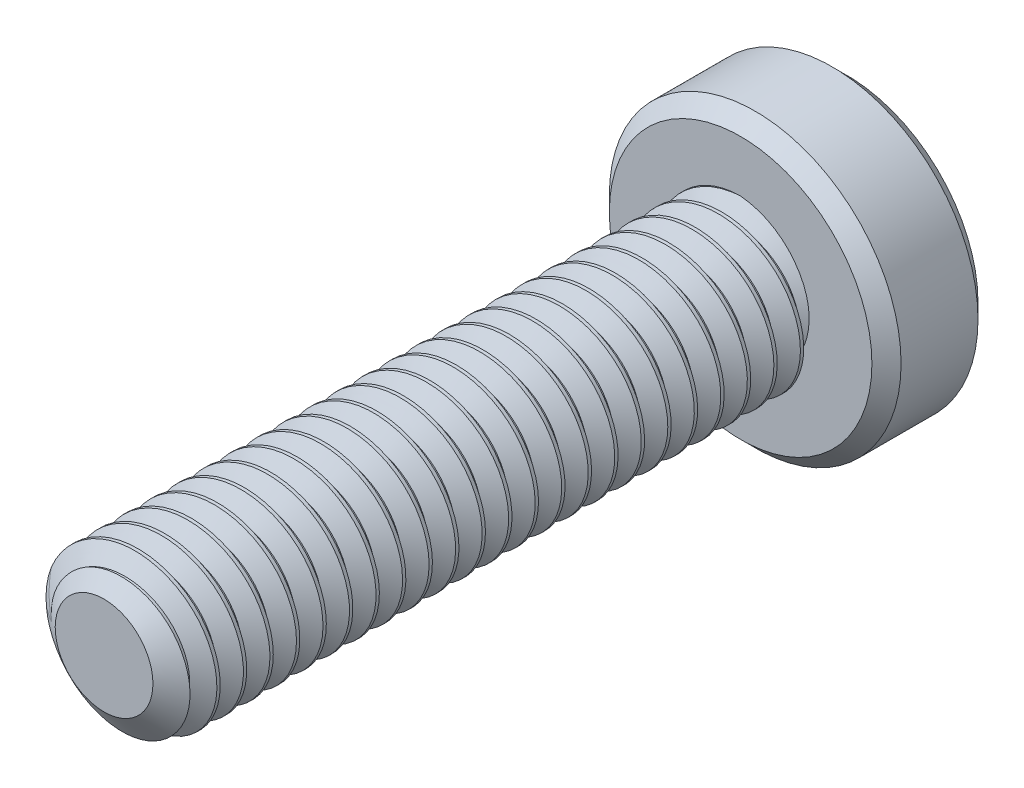
SolidWorks part; units mm, degrees
other "DetailItem1"
ref_plane "Front Plane" through (0, 0, 0) normal (0, 0, 1) x (1, 0, 0)
ref_plane "Top Plane" through (0, 0, 0) normal (0, 1, 0) x (1, 0, 0)
ref_plane "Right Plane" through (0, 0, 0) normal (1, 0, 0) x (0, 0, -1)
sketch "Sketch1" plane through (0, 0, 0) normal (0, 0, 1) x (1, 0, 0)
  circle A0 centre (0, 0) radius 1.5
  dimension "OD" = 3
extrude "Extrude1" add sketch "Sketch1" against normal blind 12
sketch "Sketch2" plane through (0, 0, 0) normal (0, 0, 1) x (1, 0, 0)
  circle A0 centre (0, 0) radius 1.5 construction
  circle A1 centre (0, 0) radius 1.5
curve "Helix/Spiral1" pitch 0.5 height 12.5 radius 1.5 centre (0, 0, 0) axis (0, 0, -1) start towards (0, 1, 0) parameters "pitch"=0.5
sketch "Sketch3" plane through (0, 0, 0) normal (1, 0, 0) x (0, 0, -1)
  line L0 (-0.4375, 1.5) -> (-0.25, 1.1752)
  line L1 (-0.25, 1.1752) -> (-0.1875, 1.1752)
  line L2 (-0.1875, 1.1752) -> (0, 1.5)
  line L3 (-0.4375, 1.5) -> (0, 1.5)
  line L4 (-0.2187, 1.5) -> (-0.2187, 1.1752) construction
  line L5 (-0.3438, 1.3376) -> (-0.0938, 1.3376) construction
  line L6 (0, 1.5) -> (0, -1.5) construction
  dimension "D1" = 0.0625
  dimension "D2" = 0.25
  dimension "D3" = 60
sweep "Cut-Sweep1" cut profiles "Sketch3" path "Helix/Spiral1" align with end faces yes
sketch "Sketch4" plane through (0, 0, 0) normal (1, 0, 0) x (0, 0, -1)
  line L0 (0.4053, 1.5) -> (0, 0.9212)
  line L1 (0, 0.9212) -> (0, 1.5)
  line L2 (0.4053, 1.5) -> (0, 1.5)
  line L3 (-0.4375, 1.5) -> (0, 1.5) construction
  line L4 (0, 0) -> (7.0209, 0) construction
  dimension "D1" = 55
  dimension "D2" = 0.254
revolve "Cut-Revolve1" cut sketch "Sketch4" angle 360 about L4
sketch "Sketch6" plane through (0, 0, -12) normal (0, 0, -1) x (-1, 0, 0)
  circle A0 centre (0, 0) radius 2.75
  dimension "head dia" = 5.5
extrude "Extrude2" add sketch "Sketch6" along normal blind 2
sketch "Sketch7" plane through (0, 0, -14) normal (0, 0, -1) x (-1, 0, 0)
  line L1 (0, 1.1547) -> (-1, 0.5774)
  line L2 (-1, 0.5774) -> (-1, -0.5774)
  line L3 (-1, -0.5774) -> (0, -1.1547)
  line L4 (0, -1.1547) -> (1, -0.5774)
  line L5 (1, -0.5774) -> (1, 0.5774)
  line L6 (1, 0.5774) -> (0, 1.1547)
  circle A0 centre (0, 0) radius 1 construction
  dimension "hex dia" = 2
extrude "Cut-Extrude1" cut sketch "Sketch7" against normal blind 1.5
sketch "Sketch8" plane through (0, 0, -14) normal (0, 0, -1) x (-1, 0, 0)
  circle A0 centre (0, 0) radius 1.1547
extrude "Cut-Extrude2" cut sketch "Sketch8" against normal through all draft 45
chamfer "Chamfer1" distance 0.275 angle 45 2 edges at (-2.75, 0, -14) (-2.75, 0, -12)
sketch "Sketch10" plane through (0, 0, -12) normal (0, 0, 1) x (1, 0, 0)
  circle A1 centre (0, 0) radius 1.5
  circle A2 centre (0, 0) radius 1.5
  dimension "D1" = 0
ref_plane "Plane1" through (0, 0, -38.1) normal (0, 0, 1) x (1, 0, 0)
extrude "partial thread" [suppressed] add sketch "Sketch10" along normal up to surface (8 mm away) separate body up to plane "Plane1"
chamfer "Chamfer2" [suppressed] distance 0.06 angle 45
combine bodies "Combine1" [suppressed] operation type add bodies to combine 107 108
sketch "Sketch9" plane through (0, 0, 0) normal (1, 0, 0) x (0, 0, -1)
  line L0 (0, 1.5) -> (0, -1.5) construction
  line L1 (1.25, 1.5) -> (1.25, -1.5) construction
  dimension "D1" = 1.25
equation "\"D3@Helix/Spiral1\" = \"screw length@Extrude1\"+\"pitch@Helix/Spiral1\""
equation "\"D1@Sketch3\" = \"pitch@Helix/Spiral1\"*.125"
equation "\"D2@Sketch3\" = \"pitch@Helix/Spiral1\"*.5"
equation "\"D1@Cut-Extrude1\" = \"hex dia@Sketch7\"*.75"
equation "\"D1@Chamfer1\" = \"head dia@Sketch6\"*.05"
equation "\"D1@Sketch9\" = \"pitch@Helix/Spiral1\"*2.5"
equation "\"D1@Chamfer2\"=\"OD@Sketch1\"*.02"
